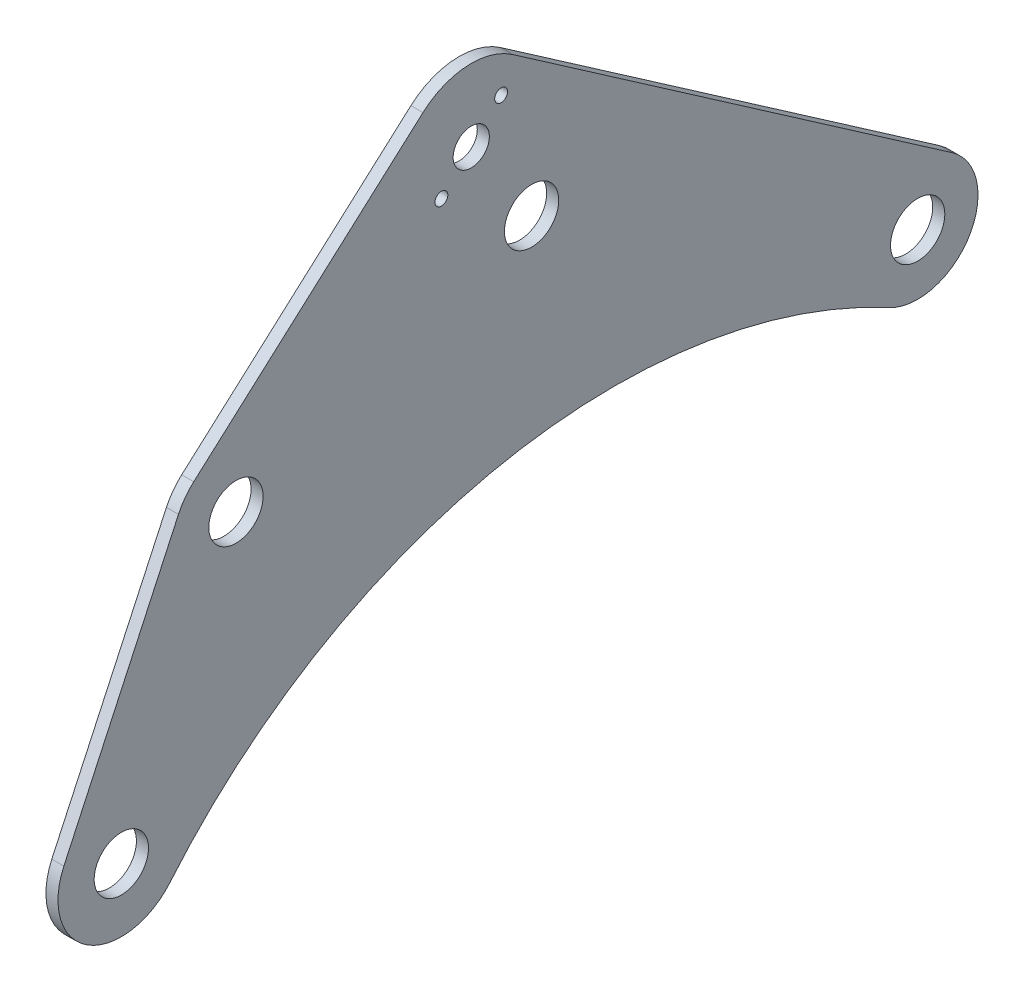
SolidWorks part; units mm, degrees
material "Acrylic (Medium-high impact)"
ref_plane "Front Plane" through (0, 0, 0) normal (0, 0, 1) x (1, 0, 0)
ref_plane "Top Plane" through (0, 0, 0) normal (0, 1, 0) x (1, 0, 0)
ref_plane "Right Plane" through (0, 0, 0) normal (1, 0, 0) x (0, 0, -1)
sketch "Sketch1" plane through (0, 0, 0) normal (1, 0, 0) x (0, 0, -1)
  line L0 (-548.7618, -304.8) -> (152.435, -304.8)
  line L1 (-192.8252, -120.65) -> (-152.4, -120.65)
  line L2 (-234.95, -162.7748) -> (-234.95, -205.5252)
  line L3 (-192.8252, -247.65) -> (-152.4, -247.65)
  line L4 (-152.4, -120.65) -> (-152.4, -247.65)
  circle A1 centre (0, 0) radius 6.35
  circle A6 centre (-419.1, -79.375) radius 9.525
  circle A7 centre (-358.775, 50.8) radius 9.525
  circle A8 centre (-203.2, 107.95) radius 9.525
  arc A9 (-234.95, -205.5252) -> (-192.8252, -247.65) centre (-192.8252, -205.5252) ccw
  arc A10 (-192.8252, -120.65) -> (-234.95, -162.7748) centre (-192.8252, -162.7748) ccw
  circle A11 centre (-358.775, -182.7754) radius 120.65
  circle A12 centre (-234.95, 155.194) radius 29.845
  point P18 (-265.9156, -17.7379)
  point P22 (-200.025, 0)
  point P23 (-358.775, -187.9263)
  point P24 (-351.6049, -184.356)
  point P25 (-345.6543, -105.8075)
  point P26 (-358.775, -182.7754)
  dimension "D1" = 12.7
  dimension "D2" = 19.05
  dimension "D3" = 42.1248
  dimension "D4" = 127
  dimension "D7" = 184.15
  dimension "D6" = 241.3
  dimension "D16" = 59.69
  dimension "D5" = 82.55
  dimension "D8" = 304.8
  dimension "D9" = 152.4
  dimension "D10" = 419.1
  dimension "D11" = 79.375
  dimension "D12" = 358.775
  dimension "D13" = 50.8
  dimension "D14" = 203.2
  dimension "D15" = 107.95
  dimension "D17" = 234.95
  dimension "D18" = 155.194
sketch "Sketch2" plane through (0, 0, 0) normal (1, 0, 0) x (0, 0, -1)
  line L1 (-449.3475, -65.3579) -> (-389.0225, 64.8171)
  line L3 (-381.0036, 75.6451) -> (-260.3541, 183.5884)
  line L5 (-213.2394, 186.5031) -> (18.0922, 26.0909)
  arc A0 (-381.0036, 75.6451) -> (-389.0225, 64.8171) centre (-358.775, 50.8) ccw
  arc A2 (-449.3475, -65.3579) -> (-393.5233, -100.7578) centre (-419.1, -79.375) ccw
  arc A4 (-213.2394, 186.5031) -> (-260.3541, 183.5884) centre (-234.95, 155.194) ccw
  arc A5 (-15.0641, -27.9488) -> (18.0922, 26.0909) centre (0, 0) ccw
  arc A8 (-393.5233, -100.7578) -> (-15.0641, -27.9488) centre (-159.6794, -296.2573) cw
  circle A12 centre (-419.1, -79.375) radius 9.525 construction
  circle A13 centre (-358.775, 50.8) radius 9.525 construction
  dimension "D1" = 33.3375
  dimension "D2" = 63.5
  dimension "D3" = 76.2
  dimension "D4" = 304.8
extrude "Boss-Extrude1" add sketch "Sketch2" along normal blind 6.35
sketch "Sketch3" plane through (6.35, 0, 0) normal (1, 0, 0) x (0, 0, -1)
  line L0 (-219.2346, 170.9094) -> (-250.6654, 139.4786) construction
  line L1 (-234.95, 155.194) -> (-234.95, 205.0182) construction
  circle A0 centre (-203.2, 107.95) radius 14.2875
  circle A1 centre (-358.775, 50.8) radius 14.2875
  circle A2 centre (-419.1, -79.375) radius 14.2875
  circle A3 centre (-234.95, 155.194) radius 9.525
  circle A4 centre (0, 0) radius 14.2875
  circle A5 centre (-250.6654, 139.4786) radius 3.3782
  circle A8 centre (-219.2346, 170.9094) radius 3.3782
  point P18 (-234.95, 155.194)
  dimension "D1" = 19.05
  dimension "D2" = 28.575
  dimension "D3" = 6.7564
  dimension "D4" = 44.45
  dimension "D5" = 45
extrude "Cut-Extrude1" cut sketch "Sketch3" against normal up to next
